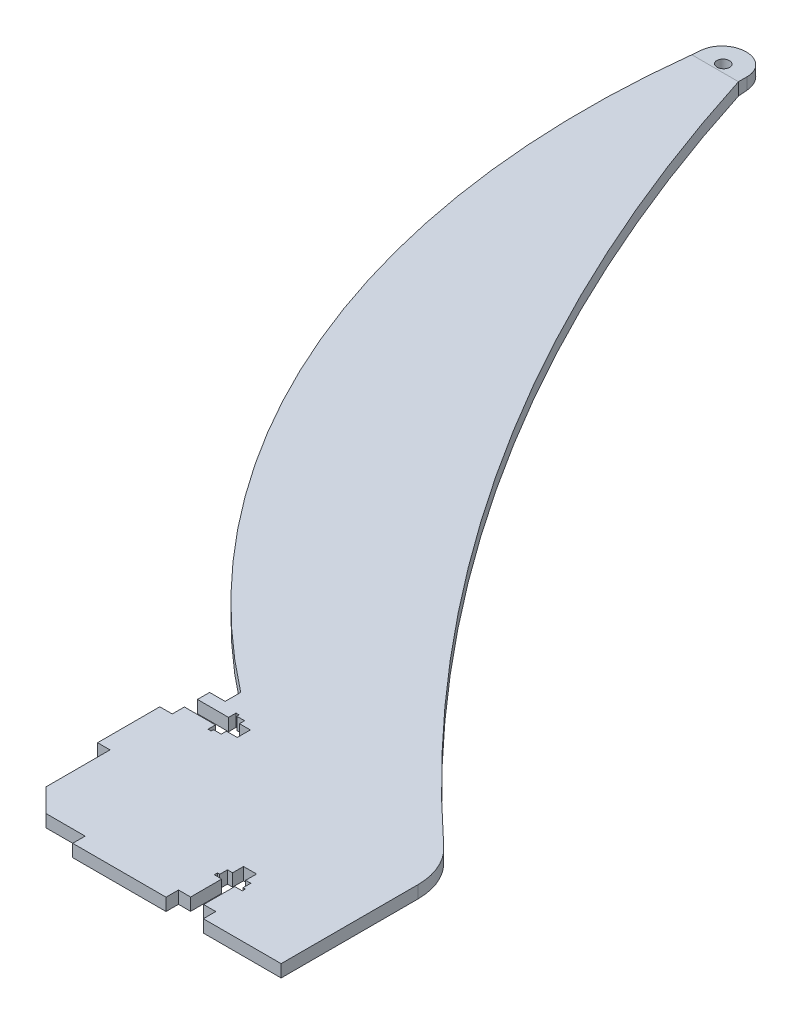
SolidWorks part; units mm, degrees
ref_plane "Front Plane" through (0, 0, 0) normal (0, 0, 1) x (1, 0, 0)
ref_plane "Top Plane" through (0, 0, 0) normal (0, 1, 0) x (1, 0, 0)
ref_plane "Right Plane" through (0, 0, 0) normal (1, 0, 0) x (0, 0, -1)
sketch "Sketch1" plane through (0, 0, 0) normal (0, 1, 0) x (1, 0, 0)
  line L0 (0, 0) -> (87, 0) construction
  line L1 (0, 0) -> (0, 100) construction
  line L2 (87, 0) -> (87, -4)
  line L3 (87, -4) -> (62, -4)
  line L4 (62, -4) -> (62, 0)
  line L5 (62, 0) -> (50, 0)
  line L6 (50, 0) -> (50, -4)
  line L7 (50, -4) -> (20, -4)
  line L8 (20, -4) -> (20, 0)
  line L9 (20, 0) -> (0, 0)
  line L10 (0, 0) -> (0, 28)
  line L11 (0, 28) -> (-4, 28)
  line L12 (-4, 28) -> (-4, 48)
  line L13 (-4, 48) -> (0, 48)
  line L14 (0, 48) -> (0, 60) construction
  line L15 (87, 0) -> (87, 40)
  line L16 (-100, 315) -> (-85, 315)
  line L17 (0, 60) -> (5, 60)
  line L18 (5, 60) -> (5, 65)
  line L19 (0, 48) -> (0, 60)
  arc A0 (80.5496, 54.7109) -> (-85, 315) centre (487.0365, 496.0365) cw
  arc A1 (5, 65) -> (-100, 315) centre (173.0904, 282.648) cw
  arc A3 (87, 40) -> (80.5496, 54.7109) centre (67, 40) ccw
  dimension "D12" = 20
  dimension "D13" = 250
  dimension "D14" = 275
  dimension "D17" = 600
  dimension "D1" = 87
  dimension "D2" = 25
  dimension "D3" = 12
  dimension "D4" = 30
  dimension "D5" = 4
  dimension "D6" = 100
  dimension "D7" = 28
  dimension "D8" = 4
  dimension "D9" = 20
  dimension "D10" = 12
  dimension "D11" = 40
  dimension "D15" = 15
  dimension "D16" = 100
  dimension "D18" = 5
  dimension "D19" = 5
extrude "Boss-Extrude1" add sketch "Sketch1" along normal blind 4
sketch "Sketch3" plane through (0, 0, -315) normal (0, 0, -1) x (-1, 0, 0)
  line L0 (85, 4) -> (100, 4) construction
  line L1 (85, 4) -> (85, 0) construction
  line L2 (85, 0) -> (100, 0) construction
  line L3 (100, 4) -> (100, 0) construction
  line L4 (85, 4) -> (100, 4)
  line L5 (85, 4) -> (85, 0)
  line L6 (85, 0) -> (100, 0)
  line L7 (100, 4) -> (100, 0)
extrude "Boss-Extrude2" add sketch "Sketch3" along normal blind 10 draft 2.5
fillet "Fillet1" 2 edges at (-85.4366, 2, -325) (-99.5634, 2, -325) type full round first side face at (-85.2183, 2, -320) second side face at (-99.7817, 2, -320) middle face at (-92.5, 2, -325)
sketch "Sketch4" plane through (0, 4, 0) normal (0, 1, 0) x (1, 0, 0)
  circle A0 centre (-92.5, 317.6215) radius 2
  arc A1 (-85.1285, 317.9433) -> (-99.8715, 317.9433) centre (-92.5, 317.6215) ccw construction
  dimension "D1" = 4
extrude "Cut-Extrude1" cut sketch "Sketch4" against normal through all
sketch "Sketch5" plane through (0, 4, 0) normal (0, 1, 0) x (1, 0, 0)
  line L0 (53.9, 0) -> (58.1, 0)
  line L1 (53.9, 0) -> (53.9, 10)
  line L2 (53.9, 17) -> (58.1, 17)
  line L3 (58.1, 0) -> (58.1, 10)
  line L4 (56, 0) -> (56, 17) construction
  line L5 (52.25, 13.5) -> (53.9, 13.5)
  line L6 (52.25, 13.5) -> (52.25, 11)
  line L7 (58.1, 13.5) -> (58.1, 17)
  line L8 (59.75, 13.5) -> (59.75, 11)
  line L9 (51.5, 11) -> (51.5, 10)
  line L10 (60.5, 10) -> (58.1, 10)
  line L12 (0, 56.1) -> (0, 51.9)
  line L13 (0, 56.1) -> (10, 56.1)
  line L14 (17, 56.1) -> (17, 51.9)
  line L15 (0, 51.9) -> (10, 51.9)
  line L16 (0, 54) -> (17, 54) construction
  line L17 (13.5, 57.75) -> (13.5, 56.1)
  line L18 (13.5, 57.75) -> (11, 57.75)
  line L19 (13.5, 51.9) -> (17, 51.9)
  line L20 (13.5, 50.25) -> (11, 50.25)
  line L21 (11, 58.5) -> (10, 58.5)
  line L22 (10, 49.5) -> (10, 51.9)
  line L23 (58.1, 10) -> (60.5, 10)
  line L24 (0, 48) -> (-4, 48) construction
  line L26 (60.5, 11) -> (60.5, 10)
  line L27 (60.5, 11) -> (59.75, 11)
  line L28 (58.1, 13.5) -> (58.1, 17)
  line L29 (59.75, 11) -> (60.5, 11)
  line L30 (53.9, 13.5) -> (52.25, 13.5)
  line L31 (52.25, 11) -> (51.5, 11)
  line L32 (58.1, 13.5) -> (59.75, 13.5)
  line L33 (53.9, 13.5) -> (53.9, 17)
  line L34 (53.9, 10) -> (51.5, 10)
  line L35 (52.25, 13.5) -> (52.25, 11)
  line L36 (53.9, 13.5) -> (53.9, 17)
  line L37 (51.5, 11) -> (52.25, 11)
  line L38 (51.5, 11) -> (51.5, 10)
  line L39 (51.5, 10) -> (53.9, 10)
  line L40 (60.5, 11) -> (60.5, 10)
  line L41 (59.75, 13.5) -> (59.75, 11)
  line L42 (59.75, 13.5) -> (58.1, 13.5)
  line L43 (53.9, 0) -> (53.9, 10)
  line L44 (58.1, 0) -> (58.1, 10)
  line L45 (53.9, 0) -> (53.9, 10)
  line L46 (58.1, 0) -> (58.1, 10)
  line L47 (52.25, 13.5) -> (53.9, 13.5)
  line L48 (52.25, 13.5) -> (52.25, 11)
  line L49 (51.5, 11) -> (51.5, 10)
  line L50 (60.5, 10) -> (58.1, 10)
  line L51 (60.5, 11) -> (60.5, 10)
  line L52 (60.5, 11) -> (59.75, 11)
  line L53 (58.1, 13.5) -> (58.1, 17)
  line L54 (59.75, 13.5) -> (59.75, 11)
  line L55 (58.1, 10) -> (60.5, 10)
  line L56 (58.1, 13.5) -> (58.1, 17)
  line L57 (53.9, 13.5) -> (52.25, 13.5)
  line L58 (59.75, 11) -> (60.5, 11)
  line L59 (58.1, 13.5) -> (59.75, 13.5)
  line L60 (52.25, 11) -> (51.5, 11)
  line L61 (53.9, 13.5) -> (53.9, 17)
  line L62 (51.5, 11) -> (52.25, 11)
  line L63 (51.5, 11) -> (51.5, 10)
  line L64 (53.9, 10) -> (51.5, 10)
  line L65 (51.5, 10) -> (53.9, 10)
  line L66 (60.5, 11) -> (60.5, 10)
  line L67 (52.25, 13.5) -> (52.25, 11)
  line L68 (53.9, 13.5) -> (53.9, 17)
  line L69 (59.75, 13.5) -> (59.75, 11)
  line L70 (59.75, 13.5) -> (58.1, 13.5)
  line L71 (53.9, 0) -> (53.9, 10)
  line L72 (58.1, 0) -> (58.1, 10)
  line L73 (50, 0) -> (62, 0) construction
  line L74 (10, 51.9) -> (10, 49.5)
  line L75 (11, 49.5) -> (10, 49.5)
  line L76 (11, 49.5) -> (11, 50.25)
  line L77 (13.5, 51.9) -> (17, 51.9)
  line L78 (11, 50.25) -> (11, 49.5)
  line L79 (13.5, 56.1) -> (13.5, 57.75)
  line L80 (11, 57.75) -> (11, 58.5)
  line L81 (13.5, 51.9) -> (13.5, 50.25)
  line L82 (13.5, 56.1) -> (17, 56.1)
  line L83 (10, 56.1) -> (10, 58.5)
  line L84 (13.5, 57.75) -> (11, 57.75)
  line L85 (13.5, 56.1) -> (17, 56.1)
  line L86 (11, 58.5) -> (11, 57.75)
  line L87 (11, 58.5) -> (10, 58.5)
  line L88 (10, 58.5) -> (10, 56.1)
  line L89 (11, 49.5) -> (10, 49.5)
  line L90 (13.5, 50.25) -> (11, 50.25)
  line L91 (13.5, 50.25) -> (13.5, 51.9)
  line L92 (0, 56.1) -> (10, 56.1)
  line L93 (0, 51.9) -> (10, 51.9)
  line L94 (0, 56.1) -> (10, 56.1)
  line L95 (0, 51.9) -> (10, 51.9)
  line L96 (13.5, 57.75) -> (13.5, 56.1)
  line L97 (13.5, 57.75) -> (11, 57.75)
  line L98 (11, 58.5) -> (10, 58.5)
  line L99 (10, 49.5) -> (10, 51.9)
  line L100 (11, 49.5) -> (10, 49.5)
  line L101 (11, 49.5) -> (11, 50.25)
  line L102 (13.5, 51.9) -> (17, 51.9)
  line L103 (13.5, 50.25) -> (11, 50.25)
  line L104 (10, 51.9) -> (10, 49.5)
  line L105 (13.5, 51.9) -> (17, 51.9)
  line L106 (13.5, 56.1) -> (13.5, 57.75)
  line L107 (11, 50.25) -> (11, 49.5)
  line L108 (13.5, 51.9) -> (13.5, 50.25)
  line L109 (11, 57.75) -> (11, 58.5)
  line L110 (13.5, 56.1) -> (17, 56.1)
  line L111 (11, 58.5) -> (11, 57.75)
  line L112 (11, 58.5) -> (10, 58.5)
  line L113 (10, 56.1) -> (10, 58.5)
  line L114 (10, 58.5) -> (10, 56.1)
  line L115 (11, 49.5) -> (10, 49.5)
  line L116 (13.5, 57.75) -> (11, 57.75)
  line L117 (13.5, 56.1) -> (17, 56.1)
  line L118 (13.5, 50.25) -> (11, 50.25)
  line L119 (13.5, 50.25) -> (13.5, 51.9)
  line L120 (0, 56.1) -> (10, 56.1)
  line L121 (0, 51.9) -> (10, 51.9)
  line M6 (50, 0) -> (62, 0)
  line M16 (0, 60) -> (0, 48)
  dimension "D2" = 4.2
  dimension "D3" = 17
  dimension "D4" = 7.5
  dimension "D5" = 4.2
  dimension "D6" = 17
  dimension "D7" = 7.5
  dimension "D8" = 2.5
  dimension "D9" = 9
  dimension "D10" = 1
  dimension "D11" = 2.5
  dimension "D12" = 9
  dimension "D13" = 1
  dimension "D14" = 10
  dimension "D15" = 10
  dimension "D16" = 6
extrude "Cut-Extrude2" cut sketch "Sketch5" against normal blind 10 contours L34 L1 L3 L10 L26 L27 L8 L32 L7 L2 L33 L5 L6 L31 L9 M6 | L83 L13 L15 L22 L75 L76 L20 L81 L19 L14 L82 L17 L18 L80 L21 M16
chamfer "Chamfer1" distance 7.5 angle 45 1 edges at (0, 2, 0)
